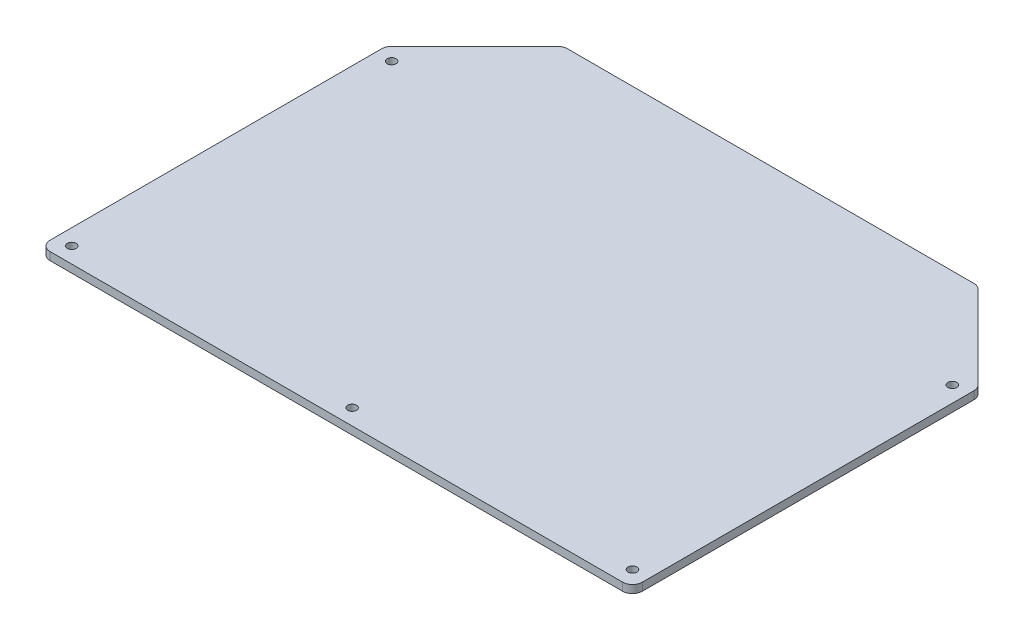
SolidWorks part; units mm, degrees
material "Acier non allié"
ref_plane "Front" through (0, 0, 0) normal (0, 0, 1) x (1, 0, 0)
ref_plane "Top" through (0, 0, 0) normal (0, 1, 0) x (1, 0, 0)
ref_plane "Right" through (0, 0, 0) normal (1, 0, 0) x (0, 0, -1)
sketch "Main scetch" plane through (0, 0, 0) normal (0, 1, 0) x (1, 0, 0)
  line L0 (-150, 0) -> (150, 0)
  line L1 (0, 0) -> (150, 0) construction
  line L2 (0, 0) -> (0, 220) construction
  line L3 (0, 220) -> (150, 220) construction
  line L4 (150, 0) -> (150, 220) construction
  line L5 (150, 0) -> (150, 175)
  line L6 (150, 175) -> (105, 220)
  line L10 (105, 220) -> (-105, 220)
  line L11 (-150, 0) -> (-150, 175)
  line L12 (-150, 175) -> (-105, 220)
  dimension "D1" = 150
  dimension "D2" = 220
  dimension "D3" = 45
  dimension "D4" = 45
extrude "Main extrusion" add sketch "Main scetch" along normal blind 4
fillet "Corner leave" radius 5 6 edges at (-150, 2, 0) (150, 2, -175) (105, 2, -220) (150, 2, 0) (-105, 2, -220) (-150, 2, -175)
sketch "Esquisse1" plane through (0, 4, 0) normal (0, 1, 0) x (1, 0, 0)
  line L0 (-145, 0) -> (145, 0) construction
  line L1 (-150, 172.9289) -> (-150, 5) construction
  line L3 (0, 0) -> (0, 62.3031) construction
  line L4 (150, 5) -> (150, 172.9289) construction
  circle A0 centre (-142, 8) radius 1
  circle A1 centre (-142, 170) radius 1
  circle A4 centre (142, 170) radius 1
  circle A5 centre (142, 8) radius 1
  circle A6 centre (0, 8) radius 1.5
  dimension "D3" = 2
  dimension "D6" = 2
  dimension "D8" = 8
  dimension "D15" = 2
  dimension "D18" = 2
  dimension "D7" = 3
  dimension "D1" = 8
  dimension "D2" = 8
  dimension "D4" = 8
  dimension "D5" = 170
  dimension "D13" = 170
  dimension "D14" = 8
  dimension "D16" = 8
  dimension "D17" = 8
hole_wizard "Dégagement M41" positions "Esquisse2" profile "Esquisse3" hole size "M4" standard "ISO" end condition through all
sketch "Esquisse2" plane through (0, 4, 0) normal (0, 1, 0) x (1, 0, 0)
  point P0 (-142, 8)
  point P3 (-142, 170)
  point P6 (142, 170)
  point P9 (142, 8)
  point P12 (0, 8)
sketch "Esquisse3" plane through (-142, 4, -8) normal (1, 0, 0) x (0, 0, 1)
  line L0 (0, 0) -> (0, 4)
  line L1 (0, 4) -> (2.25, 4)
  line L2 (2.25, 4) -> (2.25, 0)
  line L5 (2.25, 0) -> (0, 0)
  line L11 (0, -6.35) -> (0, 107.95) construction
  dimension "Diamètre du perçage jusqu'au prochain" = 4.5
  dimension "Profondeur du perçage jusqu'au prochain" = 4
equation "\"WIDTH\"= 300mm'Total width of the robot"
equation "\"LENGTH\"= 220mm'Total length of the robot"
equation "\"D1@Main scetch\" = \"WIDTH\" / 2"
equation "\"D2@Main scetch\" = \"LENGTH\""
equation "\"CUT_DEPTH\"= 45mm'Depth of the cut on the edges of the plate"
equation "\"D3@Main scetch\" = \"CUT_DEPTH\""
equation "\"D4@Main scetch\" = \"CUT_DEPTH\""
equation "\"Plate_th\"= 3mm'Thickness of the plate"
equation "\"D1\"= \"Plate_th\""
